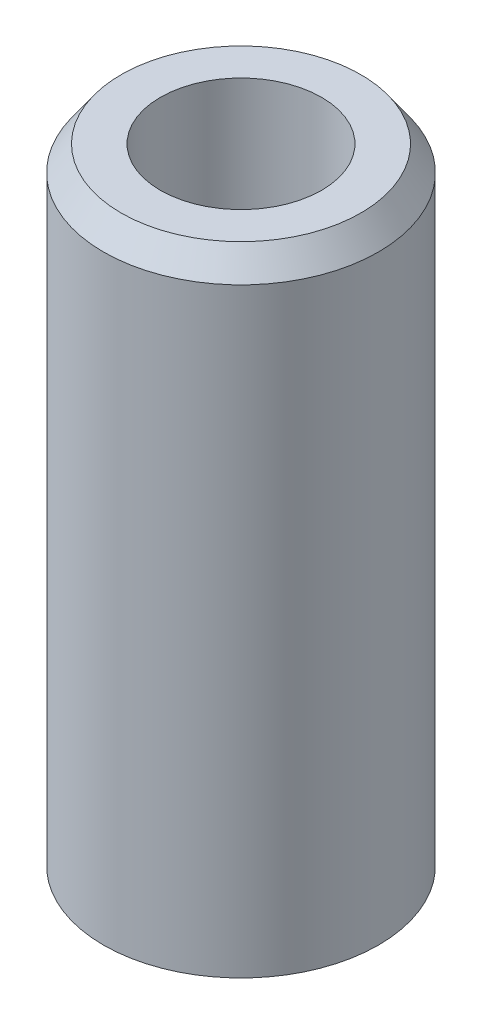
SolidWorks part; units mm, degrees
ref_plane "Front Plane" through (0, 0, 0) normal (0, 0, 1) x (1, 0, 0)
ref_plane "Top Plane" through (0, 0, 0) normal (0, 1, 0) x (1, 0, 0)
ref_plane "Right Plane" through (0, 0, 0) normal (1, 0, 0) x (0, 0, -1)
sketch "Sketch1" plane through (0, 0, 0) normal (0, 1, 0) x (1, 0, 0)
  circle A0 centre (0, 0) radius 27.5
  dimension "SHAFT_OD" = 55
extrude "Boss-Extrude1" add sketch "Sketch1" along normal blind 128.5825
sketch "Sketch2" plane through (0, 0, 0) normal (0, 1, 0) x (1, 0, 0)
  circle A0 centre (0, 0) radius 16.1242
  dimension "BORE_D" = 32.2483
extrude "Cut-Extrude1" cut sketch "Sketch2" along normal through all
chamfer "Chamfer1" distance 4.9922 angle 35.196 2 edges at (0, 128.5825, 27.5) (0, 0, 27.5) first distance on face at (0, 128.5825, 27.5) first distance on face at (0, 0, 16.1242)
